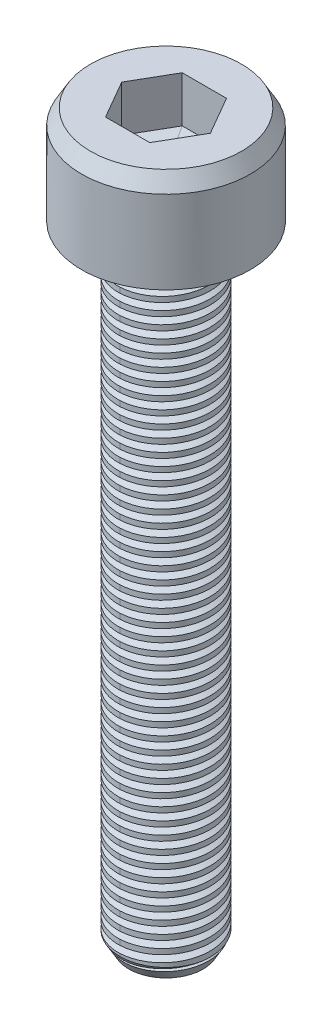
SolidWorks part; units mm, degrees
ref_plane "Front Plane" through (0, 0, 0) normal (0, 0, 1) x (1, 0, 0)
ref_plane "Top Plane" through (0, 0, 0) normal (0, 1, 0) x (1, 0, 0)
ref_plane "Right Plane" through (0, 0, 0) normal (1, 0, 0) x (0, 0, -1)
sketch "Sketch1" plane through (0, 0, 0) normal (0, 1, 0) x (1, 0, 0)
  circle A0 centre (0, 0) radius 2.75
  dimension "D1" = 5.5
extrude "Boss-Extrude1" add sketch "Sketch1" along normal blind 2.7
sketch "Sketch2" plane through (0, 2.7, 0) normal (0, 1, 0) x (1, 0, 0)
  circle A0 centre (0, 0) radius 2.75
  circle A1 centre (0, 0) radius 2.75 construction
  dimension "D1" = 5.5
extrude "Boss-Extrude2" add sketch "Sketch2" along normal blind 0.5 draft 30
sketch "Sketch5" plane through (0, 3.2, 0) normal (0, 1, 0) x (1, 0, 0)
  line L1 (1.4434, 0) -> (0.7217, 1.25)
  line L2 (0.7217, 1.25) -> (-0.7217, 1.25)
  line L3 (-0.7217, 1.25) -> (-1.4434, 0)
  line L4 (-1.4434, 0) -> (-0.7217, -1.25)
  line L5 (-0.7217, -1.25) -> (0.7217, -1.25)
  line L6 (0.7217, -1.25) -> (1.4434, 0)
  circle A0 centre (0, 0) radius 1.25 construction
  circle A1 centre (0, 0) radius 2.4613 construction
  dimension "D1" = 2.5
extrude "Cut-Extrude3" cut sketch "Sketch5" against normal blind 1.5
sketch "Sketch6" plane through (0, 1.7, 0) normal (0, 1, 0) x (1, 0, 0)
  line L0 (1.4434, 0) -> (0.7217, 1.25) construction
  line L1 (1.4434, 0) -> (0.7217, 1.25)
  line L2 (0.7217, 1.25) -> (-0.7217, 1.25)
  line L3 (-0.7217, 1.25) -> (-1.4434, 0)
  line L4 (-1.4434, 0) -> (-0.7217, -1.25)
  line L5 (-0.7217, -1.25) -> (0.7217, -1.25)
  line L6 (0.7217, -1.25) -> (1.4434, 0)
  circle A0 centre (0, 0) radius 1.25 construction
extrude "Cut-Extrude4" cut sketch "Sketch6" against normal blind 0.25 draft 80
sketch "Sketch7" plane through (0, 0, 0) normal (0, -1, 0) x (1, 0, 0)
  circle A0 centre (0, 0) radius 1.5
  circle A1 centre (0, 0) radius 2.75 construction
  dimension "D1" = 3
extrude "Boss-Extrude3" add sketch "Sketch7" along normal blind 20 contours A0
sketch "Sketch8" plane through (0, -20, 0) normal (0, -1, 0) x (1, 0, 0)
  circle A0 centre (0, 0) radius 1.5
  circle A1 centre (0, 0) radius 1.5 construction
  dimension "D1" = 3
extrude "Boss-Extrude4" add sketch "Sketch8" along normal blind 0.5 draft 30
sketch "Sketch9" plane through (0, -20.5, 0) normal (0, -1, 0) x (1, 0, 0)
  circle A0 centre (0, 0) radius 1.5
  circle A1 centre (0, 0) radius 1.2113 construction
  dimension "D1" = 3
curve "Helix/Spiral1" pitch 0.4 height 20 radius 1.5 centre (0, -20.5, 0) axis (0, 1, 0) start towards (1, 0, 0)
sketch "Sketch10" plane through (0, 0, 0) normal (0, 0, 1) x (1, 0, 0)
  line L1 (1.3037, -20.5) -> (1.5981, -20.67)
  line L2 (1.5981, -20.67) -> (1.5981, -20.33)
  line L3 (1.5981, -20.33) -> (1.3037, -20.5)
  circle A0 centre (1.5, -20.5) radius 0.0981 construction
  spline S0 degree 3 poles (1.5, -20.5) (1.5, -20.4917) (1.4219, -20.475) (1.0883, -20.45) (0.589, -20.425) (0, -20.4) (-0.589, -20.375) (-1.0883, -20.35) (-1.4219, -20.325) (-1.5391, -20.3) (-1.4219, -20.275) (-1.0883, -20.25) (-0.589, -20.225) (0, -20.2) (0.589, -20.175) (1.0883, -20.15) (1.4219, -20.125) (1.5391, -20.1) (1.4219, -20.075) (1.0883, -20.05) (0.589, -20.025) (0, -20) (-0.589, -19.975) (-1.0883, -19.95) (-1.4219, -19.925) (-1.5391, -19.9) (-1.4219, -19.875) (-1.0883, -19.85) (-0.589, -19.825) (0, -19.8) (0.589, -19.775) (1.0883, -19.75) (1.4219, -19.725) (1.5391, -19.7) (1.4219, -19.675) (1.0883, -19.65) (0.589, -19.625) (0, -19.6) (-0.589, -19.575) (-1.0883, -19.55) (-1.4219, -19.525) (-1.5391, -19.5) (-1.4219, -19.475) (-1.0883, -19.45) (-0.589, -19.425) (0, -19.4) (0.589, -19.375) (1.0883, -19.35) (1.4219, -19.325) (1.5391, -19.3) (1.4219, -19.275) (1.0883, -19.25) (0.589, -19.225) (0, -19.2) (-0.589, -19.175) (-1.0883, -19.15) (-1.4219, -19.125) (-1.5391, -19.1) (-1.4219, -19.075) (-1.0883, -19.05) (-0.589, -19.025) (0, -19) (0.589, -18.975) (1.0883, -18.95) (1.4219, -18.925) (1.5391, -18.9) (1.4219, -18.875) (1.0883, -18.85) (0.589, -18.825) (0, -18.8) (-0.589, -18.775) (-1.0883, -18.75) (-1.4219, -18.725) (-1.5391, -18.7) (-1.4219, -18.675) (-1.0883, -18.65) (-0.589, -18.625) (0, -18.6) (0.589, -18.575) (1.0883, -18.55) (1.4219, -18.525) (1.5391, -18.5) (1.4219, -18.475) (1.0883, -18.45) (0.589, -18.425) (0, -18.4) (-0.589, -18.375) (-1.0883, -18.35) (-1.4219, -18.325) (-1.5391, -18.3) (-1.4219, -18.275) (-1.0883, -18.25) (-0.589, -18.225) (0, -18.2) (0.589, -18.175) (1.0883, -18.15) (1.4219, -18.125) (1.5391, -18.1) (1.4219, -18.075) (1.0883, -18.05) (0.589, -18.025) (0, -18) (-0.589, -17.975) (-1.0883, -17.95) (-1.4219, -17.925) (-1.5391, -17.9) (-1.4219, -17.875) (-1.0883, -17.85) (-0.589, -17.825) (0, -17.8) (0.589, -17.775) (1.0883, -17.75) (1.4219, -17.725) (1.5391, -17.7) (1.4219, -17.675) (1.0883, -17.65) (0.589, -17.625) (0, -17.6) (-0.589, -17.575) (-1.0883, -17.55) (-1.4219, -17.525) (-1.5391, -17.5) (-1.4219, -17.475) (-1.0883, -17.45) (-0.589, -17.425) (0, -17.4) (0.589, -17.375) (1.0883, -17.35) (1.4219, -17.325) (1.5391, -17.3) (1.4219, -17.275) (1.0883, -17.25) (0.589, -17.225) (0, -17.2) (-0.589, -17.175) (-1.0883, -17.15) (-1.4219, -17.125) (-1.5391, -17.1) (-1.4219, -17.075) (-1.0883, -17.05) (-0.589, -17.025) (0, -17) (0.589, -16.975) (1.0883, -16.95) (1.4219, -16.925) (1.5391, -16.9) (1.4219, -16.875) (1.0883, -16.85) (0.589, -16.825) (0, -16.8) (-0.589, -16.775) (-1.0883, -16.75) (-1.4219, -16.725) (-1.5391, -16.7) (-1.4219, -16.675) (-1.0883, -16.65) (-0.589, -16.625) (0, -16.6) (0.589, -16.575) (1.0883, -16.55) (1.4219, -16.525) (1.5391, -16.5) (1.4219, -16.475) (1.0883, -16.45) (0.589, -16.425) (0, -16.4) (-0.589, -16.375) (-1.0883, -16.35) (-1.4219, -16.325) (-1.5391, -16.3) (-1.4219, -16.275) (-1.0883, -16.25) (-0.589, -16.225) (0, -16.2) (0.589, -16.175) (1.0883, -16.15) (1.4219, -16.125) (1.5391, -16.1) (1.4219, -16.075) (1.0883, -16.05) (0.589, -16.025) (0, -16) (-0.589, -15.975) (-1.0883, -15.95) (-1.4219, -15.925) (-1.5391, -15.9) (-1.4219, -15.875) (-1.0883, -15.85) (-0.589, -15.825) (0, -15.8) (0.589, -15.775) (1.0883, -15.75) (1.4219, -15.725) (1.5391, -15.7) (1.4219, -15.675) (1.0883, -15.65) (0.589, -15.625) (0, -15.6) (-0.589, -15.575) (-1.0883, -15.55) (-1.4219, -15.525) (-1.5391, -15.5) (-1.4219, -15.475) (-1.0883, -15.45) (-0.589, -15.425) (0, -15.4) (0.589, -15.375) (1.0883, -15.35) (1.4219, -15.325) (1.5391, -15.3) (1.4219, -15.275) (1.0883, -15.25) (0.589, -15.225) (0, -15.2) (-0.589, -15.175) (-1.0883, -15.15) (-1.4219, -15.125) (-1.5391, -15.1) (-1.4219, -15.075) (-1.0883, -15.05) (-0.589, -15.025) (0, -15) (0.589, -14.975) (1.0883, -14.95) (1.4219, -14.925) (1.5391, -14.9) (1.4219, -14.875) (1.0883, -14.85) (0.589, -14.825) (0, -14.8) (-0.589, -14.775) (-1.0883, -14.75) (-1.4219, -14.725) (-1.5391, -14.7) (-1.4219, -14.675) (-1.0883, -14.65) (-0.589, -14.625) (0, -14.6) (0.589, -14.575) (1.0883, -14.55) (1.4219, -14.525) (1.5391, -14.5) (1.4219, -14.475) (1.0883, -14.45) (0.589, -14.425) (0, -14.4) (-0.589, -14.375) (-1.0883, -14.35) (-1.4219, -14.325) (-1.5391, -14.3) (-1.4219, -14.275) (-1.0883, -14.25) (-0.589, -14.225) (0, -14.2) (0.589, -14.175) (1.0883, -14.15) (1.4219, -14.125) (1.5391, -14.1) (1.4219, -14.075) (1.0883, -14.05) (0.589, -14.025) (0, -14) (-0.589, -13.975) (-1.0883, -13.95) (-1.4219, -13.925) (-1.5391, -13.9) (-1.4219, -13.875) (-1.0883, -13.85) (-0.589, -13.825) (0, -13.8) (0.589, -13.775) (1.0883, -13.75) (1.4219, -13.725) (1.5391, -13.7) (1.4219, -13.675) (1.0883, -13.65) (0.589, -13.625) (0, -13.6) (-0.589, -13.575) (-1.0883, -13.55) (-1.4219, -13.525) (-1.5391, -13.5) (-1.4219, -13.475) (-1.0883, -13.45) (-0.589, -13.425) (0, -13.4) (0.589, -13.375) (1.0883, -13.35) (1.4219, -13.325) (1.5391, -13.3) (1.4219, -13.275) (1.0883, -13.25) (0.589, -13.225) (0, -13.2) (-0.589, -13.175) (-1.0883, -13.15) (-1.4219, -13.125) (-1.5391, -13.1) (-1.4219, -13.075) (-1.0883, -13.05) (-0.589, -13.025) (0, -13) (0.589, -12.975) (1.0883, -12.95) (1.4219, -12.925) (1.5391, -12.9) (1.4219, -12.875) (1.0883, -12.85) (0.589, -12.825) (0, -12.8) (-0.589, -12.775) (-1.0883, -12.75) (-1.4219, -12.725) (-1.5391, -12.7) (-1.4219, -12.675) (-1.0883, -12.65) (-0.589, -12.625) (0, -12.6) (0.589, -12.575) (1.0883, -12.55) (1.4219, -12.525) (1.5391, -12.5) (1.4219, -12.475) (1.0883, -12.45) (0.589, -12.425) (0, -12.4) (-0.589, -12.375) (-1.0883, -12.35) (-1.4219, -12.325) (-1.5391, -12.3) (-1.4219, -12.275) (-1.0883, -12.25) (-0.589, -12.225) (0, -12.2) (0.589, -12.175) (1.0883, -12.15) (1.4219, -12.125) (1.5391, -12.1) (1.4219, -12.075) (1.0883, -12.05) (0.589, -12.025) (0, -12) (-0.589, -11.975) (-1.0883, -11.95) (-1.4219, -11.925) (-1.5391, -11.9) (-1.4219, -11.875) (-1.0883, -11.85) (-0.589, -11.825) (0, -11.8) (0.589, -11.775) (1.0883, -11.75) (1.4219, -11.725) (1.5391, -11.7) (1.4219, -11.675) (1.0883, -11.65) (0.589, -11.625) (0, -11.6) (-0.589, -11.575) (-1.0883, -11.55) (-1.4219, -11.525) (-1.5391, -11.5) (-1.4219, -11.475) (-1.0883, -11.45) (-0.589, -11.425) (0, -11.4) (0.589, -11.375) (1.0883, -11.35) (1.4219, -11.325) (1.5391, -11.3) (1.4219, -11.275) (1.0883, -11.25) (0.589, -11.225) (0, -11.2) (-0.589, -11.175) (-1.0883, -11.15) (-1.4219, -11.125) (-1.5391, -11.1) (-1.4219, -11.075) (-1.0883, -11.05) (-0.589, -11.025) (0, -11) (0.589, -10.975) (1.0883, -10.95) (1.4219, -10.925) (1.5391, -10.9) (1.4219, -10.875) (1.0883, -10.85) (0.589, -10.825) (0, -10.8) (-0.589, -10.775) (-1.0883, -10.75) (-1.4219, -10.725) (-1.5391, -10.7) (-1.4219, -10.675) (-1.0883, -10.65) (-0.589, -10.625) (0, -10.6) (0.589, -10.575) (1.0883, -10.55) (1.4219, -10.525) (1.5391, -10.5) (1.4219, -10.475) (1.0883, -10.45) (0.589, -10.425) (0, -10.4) (-0.589, -10.375) (-1.0883, -10.35) (-1.4219, -10.325) (-1.5391, -10.3) (-1.4219, -10.275) (-1.0883, -10.25) (-0.589, -10.225) (0, -10.2) (0.589, -10.175) (1.0883, -10.15) (1.4219, -10.125) (1.5391, -10.1) (1.4219, -10.075) (1.0883, -10.05) (0.589, -10.025) (0, -10) (-0.589, -9.975) (-1.0883, -9.95) (-1.4219, -9.925) (-1.5391, -9.9) (-1.4219, -9.875) (-1.0883, -9.85) (-0.589, -9.825) (0, -9.8) (0.589, -9.775) (1.0883, -9.75) (1.4219, -9.725) (1.5391, -9.7) (1.4219, -9.675) (1.0883, -9.65) (0.589, -9.625) (0, -9.6) (-0.589, -9.575) (-1.0883, -9.55) (-1.4219, -9.525) (-1.5391, -9.5) (-1.4219, -9.475) (-1.0883, -9.45) (-0.589, -9.425) (0, -9.4) (0.589, -9.375) (1.0883, -9.35) (1.4219, -9.325) (1.5391, -9.3) (1.4219, -9.275) (1.0883, -9.25) (0.589, -9.225) (0, -9.2) (-0.589, -9.175) (-1.0883, -9.15) (-1.4219, -9.125) (-1.5391, -9.1) (-1.4219, -9.075) (-1.0883, -9.05) (-0.589, -9.025) (0, -9) (0.589, -8.975) (1.0883, -8.95) (1.4219, -8.925) (1.5391, -8.9) (1.4219, -8.875) (1.0883, -8.85) (0.589, -8.825) (0, -8.8) (-0.589, -8.775) (-1.0883, -8.75) (-1.4219, -8.725) (-1.5391, -8.7) (-1.4219, -8.675) (-1.0883, -8.65) (-0.589, -8.625) (0, -8.6) (0.589, -8.575) (1.0883, -8.55) (1.4219, -8.525) (1.5391, -8.5) (1.4219, -8.475) (1.0883, -8.45) (0.589, -8.425) (0, -8.4) (-0.589, -8.375) (-1.0883, -8.35) (-1.4219, -8.325) (-1.5391, -8.3) (-1.4219, -8.275) (-1.0883, -8.25) (-0.589, -8.225) (0, -8.2) (0.589, -8.175) (1.0883, -8.15) (1.4219, -8.125) (1.5391, -8.1) (1.4219, -8.075) (1.0883, -8.05) (0.589, -8.025) (0, -8) (-0.589, -7.975) (-1.0883, -7.95) (-1.4219, -7.925) (-1.5391, -7.9) (-1.4219, -7.875) (-1.0883, -7.85) (-0.589, -7.825) (0, -7.8) (0.589, -7.775) (1.0883, -7.75) (1.4219, -7.725) (1.5391, -7.7) (1.4219, -7.675) (1.0883, -7.65) (0.589, -7.625) (0, -7.6) (-0.589, -7.575) (-1.0883, -7.55) (-1.4219, -7.525) (-1.5391, -7.5) (-1.4219, -7.475) (-1.0883, -7.45) (-0.589, -7.425) (0, -7.4) (0.589, -7.375) (1.0883, -7.35) (1.4219, -7.325) (1.5391, -7.3) (1.4219, -7.275) (1.0883, -7.25) (0.589, -7.225) (0, -7.2) (-0.589, -7.175) (-1.0883, -7.15) (-1.4219, -7.125) (-1.5391, -7.1) (-1.4219, -7.075) (-1.0883, -7.05) (-0.589, -7.025) (0, -7) (0.589, -6.975) (1.0883, -6.95) (1.4219, -6.925) (1.5391, -6.9) (1.4219, -6.875) (1.0883, -6.85) (0.589, -6.825) (0, -6.8) (-0.589, -6.775) (-1.0883, -6.75) (-1.4219, -6.725) (-1.5391, -6.7) (-1.4219, -6.675) (-1.0883, -6.65) (-0.589, -6.625) (0, -6.6) (0.589, -6.575) (1.0883, -6.55) (1.4219, -6.525) (1.5391, -6.5) (1.4219, -6.475) (1.0883, -6.45) (0.589, -6.425) (0, -6.4) (-0.589, -6.375) (-1.0883, -6.35) (-1.4219, -6.325) (-1.5391, -6.3) (-1.4219, -6.275) (-1.0883, -6.25) (-0.589, -6.225) (0, -6.2) (0.589, -6.175) (1.0883, -6.15) (1.4219, -6.125) (1.5391, -6.1) (1.4219, -6.075) (1.0883, -6.05) (0.589, -6.025) (0, -6) (-0.589, -5.975) (-1.0883, -5.95) (-1.4219, -5.925) (-1.5391, -5.9) (-1.4219, -5.875) (-1.0883, -5.85) (-0.589, -5.825) (0, -5.8) (0.589, -5.775) (1.0883, -5.75) (1.4219, -5.725) (1.5391, -5.7) (1.4219, -5.675) (1.0883, -5.65) (0.589, -5.625) (0, -5.6) (-0.589, -5.575) (-1.0883, -5.55) (-1.4219, -5.525) (-1.5391, -5.5) (-1.4219, -5.475) (-1.0883, -5.45) (-0.589, -5.425) (0, -5.4) (0.589, -5.375) (1.0883, -5.35) (1.4219, -5.325) (1.5391, -5.3) (1.4219, -5.275) (1.0883, -5.25) (0.589, -5.225) (0, -5.2) (-0.589, -5.175) (-1.0883, -5.15) (-1.4219, -5.125) (-1.5391, -5.1) (-1.4219, -5.075) (-1.0883, -5.05) (-0.589, -5.025) (0, -5) (0.589, -4.975) (1.0883, -4.95) (1.4219, -4.925) (1.5391, -4.9) (1.4219, -4.875) (1.0883, -4.85) (0.589, -4.825) (0, -4.8) (-0.589, -4.775) (-1.0883, -4.75) (-1.4219, -4.725) (-1.5391, -4.7) (-1.4219, -4.675) (-1.0883, -4.65) (-0.589, -4.625) (0, -4.6) (0.589, -4.575) (1.0883, -4.55) (1.4219, -4.525) (1.5391, -4.5) (1.4219, -4.475) (1.0883, -4.45) (0.589, -4.425) (0, -4.4) (-0.589, -4.375) (-1.0883, -4.35) (-1.4219, -4.325) (-1.5391, -4.3) (-1.4219, -4.275) (-1.0883, -4.25) (-0.589, -4.225) (0, -4.2) (0.589, -4.175) (1.0883, -4.15) (1.4219, -4.125) (1.5391, -4.1) (1.4219, -4.075) (1.0883, -4.05) (0.589, -4.025) (0, -4) (-0.589, -3.975) (-1.0883, -3.95) (-1.4219, -3.925) (-1.5391, -3.9) (-1.4219, -3.875) (-1.0883, -3.85) (-0.589, -3.825) (0, -3.8) (0.589, -3.775) (1.0883, -3.75) (1.4219, -3.725) (1.5391, -3.7) (1.4219, -3.675) (1.0883, -3.65) (0.589, -3.625) (0, -3.6) (-0.589, -3.575) (-1.0883, -3.55) (-1.4219, -3.525) (-1.5391, -3.5) (-1.4219, -3.475) (-1.0883, -3.45) (-0.589, -3.425) (0, -3.4) (0.589, -3.375) (1.0883, -3.35) (1.4219, -3.325) (1.5391, -3.3) (1.4219, -3.275) (1.0883, -3.25) (0.589, -3.225) (0, -3.2) (-0.589, -3.175) (-1.0883, -3.15) (-1.4219, -3.125) (-1.5391, -3.1) (-1.4219, -3.075) (-1.0883, -3.05) (-0.589, -3.025) (0, -3) (0.589, -2.975) (1.0883, -2.95) (1.4219, -2.925) (1.5391, -2.9) (1.4219, -2.875) (1.0883, -2.85) (0.589, -2.825) (0, -2.8) (-0.589, -2.775) (-1.0883, -2.75) (-1.4219, -2.725) (-1.5391, -2.7) (-1.4219, -2.675) (-1.0883, -2.65) (-0.589, -2.625) (0, -2.6) (0.589, -2.575) (1.0883, -2.55) (1.4219, -2.525) (1.5391, -2.5) (1.4219, -2.475) (1.0883, -2.45) (0.589, -2.425) (0, -2.4) (-0.589, -2.375) (-1.0883, -2.35) (-1.4219, -2.325) (-1.5391, -2.3) (-1.4219, -2.275) (-1.0883, -2.25) (-0.589, -2.225) (0, -2.2) (0.589, -2.175) (1.0883, -2.15) (1.4219, -2.125) (1.5391, -2.1) (1.4219, -2.075) (1.0883, -2.05) (0.589, -2.025) (0, -2) (-0.589, -1.975) (-1.0883, -1.95) (-1.4219, -1.925) (-1.5391, -1.9) (-1.4219, -1.875) (-1.0883, -1.85) (-0.589, -1.825) (0, -1.8) (0.589, -1.775) (1.0883, -1.75) (1.4219, -1.725) (1.5391, -1.7) (1.4219, -1.675) (1.0883, -1.65) (0.589, -1.625) (0, -1.6) (-0.589, -1.575) (-1.0883, -1.55) (-1.4219, -1.525) (-1.5391, -1.5) (-1.4219, -1.475) (-1.0883, -1.45) (-0.589, -1.425) (0, -1.4) (0.589, -1.375) (1.0883, -1.35) (1.4219, -1.325) (1.5391, -1.3) (1.4219, -1.275) (1.0883, -1.25) (0.589, -1.225) (0, -1.2) (-0.589, -1.175) (-1.0883, -1.15) (-1.4219, -1.125) (-1.5391, -1.1) (-1.4219, -1.075) (-1.0883, -1.05) (-0.589, -1.025) (0, -1) (0.589, -0.975) (1.0883, -0.95) (1.4219, -0.925) (1.5391, -0.9) (1.4219, -0.875) (1.0883, -0.85) (0.589, -0.825) (0, -0.8) (-0.589, -0.775) (-1.0883, -0.75) (-1.4219, -0.725) (-1.5391, -0.7) (-1.4219, -0.675) (-1.0883, -0.65) (-0.589, -0.625) (0, -0.6) (0.589, -0.575) (1.0883, -0.55) (1.4219, -0.525) (1.5, -0.5083) (1.5, -0.5) knots 0 0 0 0 0.00125 0.0025 0.00375 0.005 0.00625 0.0075 0.00875 0.01 0.01125 0.0125 0.01375 0.015 0.01625 0.0175 0.01875 0.02 0.02125 0.0225 0.02375 0.025 0.02625 0.0275 0.02875 0.03 0.03125 0.0325 0.03375 0.035 0.03625 0.0375 0.03875 0.04 0.04125 0.0425 0.04375 0.045 0.04625 0.0475 0.04875 0.05 0.05125 0.0525 0.05375 0.055 0.05625 0.0575 0.05875 0.06 0.06125 0.0625 0.06375 0.065 0.06625 0.0675 0.06875 0.07 0.07125 0.0725 0.07375 0.075 0.07625 0.0775 0.07875 0.08 0.08125 0.0825 0.08375 0.085 0.08625 0.0875 0.08875 0.09 0.09125 0.0925 0.09375 0.095 0.09625 0.0975 0.09875 0.1 0.10125 0.1025 0.10375 0.105 0.10625 0.1075 0.10875 0.11 0.11125 0.1125 0.11375 0.115 0.11625 0.1175 0.11875 0.12 0.12125 0.1225 0.12375 0.125 0.12625 0.1275 0.12875 0.13 0.13125 0.1325 0.13375 0.135 0.13625 0.1375 0.13875 0.14 0.14125 0.1425 0.14375 0.145 0.14625 0.1475 0.14875 0.15 0.15125 0.1525 0.15375 0.155 0.15625 0.1575 0.15875 0.16 0.16125 0.1625 0.16375 0.165 0.16625 0.1675 0.16875 0.17 0.17125 0.1725 0.17375 0.175 0.17625 0.1775 0.17875 0.18 0.18125 0.1825 0.18375 0.185 0.18625 0.1875 0.18875 0.19 0.19125 0.1925 0.19375 0.195 0.19625 0.1975 0.19875 0.2 0.20125 0.2025 0.20375 0.205 0.20625 0.2075 0.20875 0.21 0.21125 0.2125 0.21375 0.215 0.21625 0.2175 0.21875 0.22 0.22125 0.2225 0.22375 0.225 0.22625 0.2275 0.22875 0.23 0.23125 0.2325 0.23375 0.235 0.23625 0.2375 0.23875 0.24 0.24125 0.2425 0.24375 0.245 0.24625 0.2475 0.24875 0.25 0.25125 0.2525 0.25375 0.255 0.25625 0.2575 0.25875 0.26 0.26125 0.2625 0.26375 0.265 0.26625 0.2675 0.26875 0.27 0.27125 0.2725 0.27375 0.275 0.27625 0.2775 0.27875 0.28 0.28125 0.2825 0.28375 0.285 0.28625 0.2875 0.28875 0.29 0.29125 0.2925 0.29375 0.295 0.29625 0.2975 0.29875 0.3 0.30125 0.3025 0.30375 0.305 0.30625 0.3075 0.30875 0.31 0.31125 0.3125 0.31375 0.315 0.31625 0.3175 0.31875 0.32 0.32125 0.3225 0.32375 0.325 0.32625 0.3275 0.32875 0.33 0.33125 0.3325 0.33375 0.335 0.33625 0.3375 0.33875 0.34 0.34125 0.3425 0.34375 0.345 0.34625 0.3475 0.34875 0.35 0.35125 0.3525 0.35375 0.355 0.35625 0.3575 0.35875 0.36 0.36125 0.3625 0.36375 0.365 0.36625 0.3675 0.36875 0.37 0.37125 0.3725 0.37375 0.375 0.37625 0.3775 0.37875 0.38 0.38125 0.3825 0.38375 0.385 0.38625 0.3875 0.38875 0.39 0.39125 0.3925 0.39375 0.395 0.39625 0.3975 0.39875 0.4 0.40125 0.4025 0.40375 0.405 0.40625 0.4075 0.40875 0.41 0.41125 0.4125 0.41375 0.415 0.41625 0.4175 0.41875 0.42 0.42125 0.4225 0.42375 0.425 0.42625 0.4275 0.42875 0.43 0.43125 0.4325 0.43375 0.435 0.43625 0.4375 0.43875 0.44 0.44125 0.4425 0.44375 0.445 0.44625 0.4475 0.44875 0.45 0.45125 0.4525 0.45375 0.455 0.45625 0.4575 0.45875 0.46 0.46125 0.4625 0.46375 0.465 0.46625 0.4675 0.46875 0.47 0.47125 0.4725 0.47375 0.475 0.47625 0.4775 0.47875 0.48 0.48125 0.4825 0.48375 0.485 0.48625 0.4875 0.48875 0.49 0.49125 0.4925 0.49375 0.495 0.49625 0.4975 0.49875 0.5 0.50125 0.5025 0.50375 0.505 0.50625 0.5075 0.50875 0.51 0.51125 0.5125 0.51375 0.515 0.51625 0.5175 0.51875 0.52 0.52125 0.5225 0.52375 0.525 0.52625 0.5275 0.52875 0.53 0.53125 0.5325 0.53375 0.535 0.53625 0.5375 0.53875 0.54 0.54125 0.5425 0.54375 0.545 0.54625 0.5475 0.54875 0.55 0.55125 0.5525 0.55375 0.555 0.55625 0.5575 0.55875 0.56 0.56125 0.5625 0.56375 0.565 0.56625 0.5675 0.56875 0.57 0.57125 0.5725 0.57375 0.575 0.57625 0.5775 0.57875 0.58 0.58125 0.5825 0.58375 0.585 0.58625 0.5875 0.58875 0.59 0.59125 0.5925 0.59375 0.595 0.59625 0.5975 0.59875 0.6 0.60125 0.6025 0.60375 0.605 0.60625 0.6075 0.60875 0.61 0.61125 0.6125 0.61375 0.615 0.61625 0.6175 0.61875 0.62 0.62125 0.6225 0.62375 0.625 0.62625 0.6275 0.62875 0.63 0.63125 0.6325 0.63375 0.635 0.63625 0.6375 0.63875 0.64 0.64125 0.6425 0.64375 0.645 0.64625 0.6475 0.64875 0.65 0.65125 0.6525 0.65375 0.655 0.65625 0.6575 0.65875 0.66 0.66125 0.6625 0.66375 0.665 0.66625 0.6675 0.66875 0.67 0.67125 0.6725 0.67375 0.675 0.67625 0.6775 0.67875 0.68 0.68125 0.6825 0.68375 0.685 0.68625 0.6875 0.68875 0.69 0.69125 0.6925 0.69375 0.695 0.69625 0.6975 0.69875 0.7 0.70125 0.7025 0.70375 0.705 0.70625 0.7075 0.70875 0.71 0.71125 0.7125 0.71375 0.715 0.71625 0.7175 0.71875 0.72 0.72125 0.7225 0.72375 0.725 0.72625 0.7275 0.72875 0.73 0.73125 0.7325 0.73375 0.735 0.73625 0.7375 0.73875 0.74 0.74125 0.7425 0.74375 0.745 0.74625 0.7475 0.74875 0.75 0.75125 0.7525 0.75375 0.755 0.75625 0.7575 0.75875 0.76 0.76125 0.7625 0.76375 0.765 0.76625 0.7675 0.76875 0.77 0.77125 0.7725 0.77375 0.775 0.77625 0.7775 0.77875 0.78 0.78125 0.7825 0.78375 0.785 0.78625 0.7875 0.78875 0.79 0.79125 0.7925 0.79375 0.795 0.79625 0.7975 0.79875 0.8 0.80125 0.8025 0.80375 0.805 0.80625 0.8075 0.80875 0.81 0.81125 0.8125 0.81375 0.815 0.81625 0.8175 0.81875 0.82 0.82125 0.8225 0.82375 0.825 0.82625 0.8275 0.82875 0.83 0.83125 0.8325 0.83375 0.835 0.83625 0.8375 0.83875 0.84 0.84125 0.8425 0.84375 0.845 0.84625 0.8475 0.84875 0.85 0.85125 0.8525 0.85375 0.855 0.85625 0.8575 0.85875 0.86 0.86125 0.8625 0.86375 0.865 0.86625 0.8675 0.86875 0.87 0.87125 0.8725 0.87375 0.875 0.87625 0.8775 0.87875 0.88 0.88125 0.8825 0.88375 0.885 0.88625 0.8875 0.88875 0.89 0.89125 0.8925 0.89375 0.895 0.89625 0.8975 0.89875 0.9 0.90125 0.9025 0.90375 0.905 0.90625 0.9075 0.90875 0.91 0.91125 0.9125 0.91375 0.915 0.91625 0.9175 0.91875 0.92 0.92125 0.9225 0.92375 0.925 0.92625 0.9275 0.92875 0.93 0.93125 0.9325 0.93375 0.935 0.93625 0.9375 0.93875 0.94 0.94125 0.9425 0.94375 0.945 0.94625 0.9475 0.94875 0.95 0.95125 0.9525 0.95375 0.955 0.95625 0.9575 0.95875 0.96 0.96125 0.9625 0.96375 0.965 0.96625 0.9675 0.96875 0.97 0.97125 0.9725 0.97375 0.975 0.97625 0.9775 0.97875 0.98 0.98125 0.9825 0.98375 0.985 0.98625 0.9875 0.98875 0.99 0.99125 0.9925 0.99375 0.995 0.99625 0.9975 0.99875 1 1 1 1 construction
  dimension "D1" = 0.1963
  dimension "D2" = 1.3037
sweep "Cut-Sweep1" cut profiles "Sketch10" path "Helix/Spiral1"
